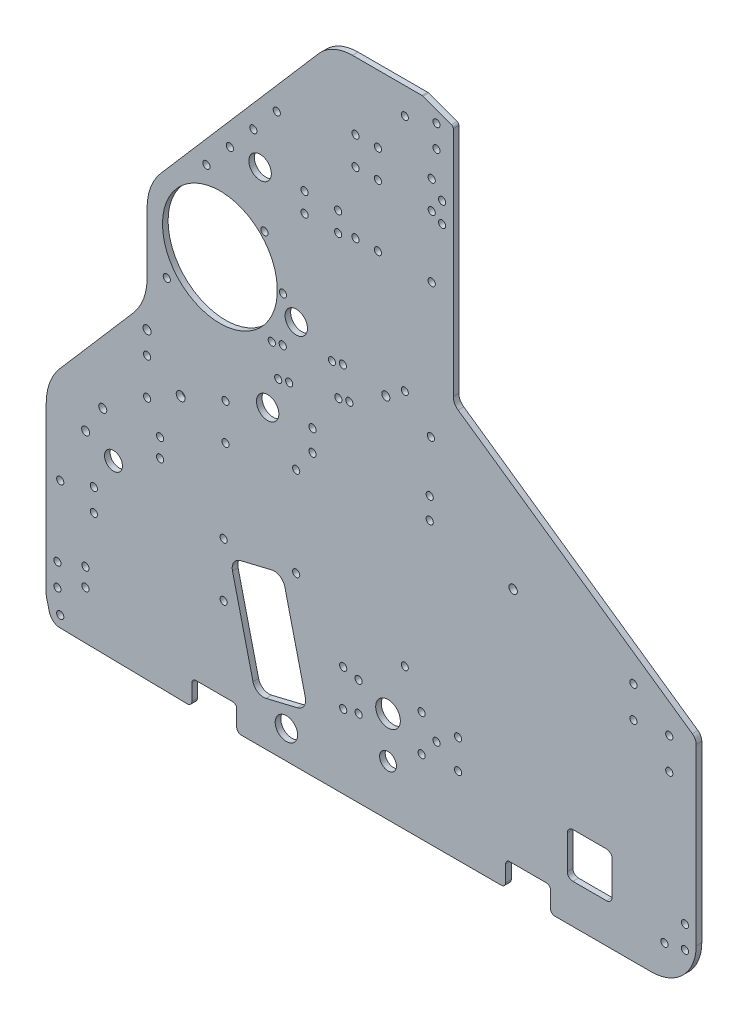
SolidWorks part; units mm, degrees
ref_plane "Front Plane" through (0, 0, 0) normal (0, 0, 1) x (1, 0, 0)
ref_plane "Top Plane" through (0, 0, 0) normal (0, 1, 0) x (1, 0, 0)
ref_plane "Right Plane" through (0, 0, 0) normal (1, 0, 0) x (0, 0, -1)
sketch "Sketch1" plane through (0, 0, 0) normal (0, 0, 1) x (1, 0, 0)
  line L0 (82.55, -20.32) -> (82.55, -6.35)
  line L2 (0, 0) -> (0, 157.48)
  line L4 (368.3, -20.32) -> (368.3, 106.68)
  line L5 (82.55, -6.35) -> (107.95, -6.35)
  line L6 (107.95, -6.35) -> (107.95, -20.32)
  line L7 (107.95, -20.32) -> (260.35, -20.32)
  line L8 (260.35, -20.32) -> (260.35, -6.35)
  line L9 (260.35, -6.35) -> (285.75, -6.35)
  line L10 (285.75, -6.35) -> (285.75, -20.32)
  line L11 (285.75, -20.32) -> (368.3, -20.32)
  line L12 (361.95, 12.7) -> (368.3, 12.7) construction
  line L13 (0, 0) -> (6.35, 0) construction
  line L14 (0.1896, -7.8901) -> (1.7771, -14.2401)
  line L15 (7.8295, -19.0491) -> (82.55, -20.32)
  line L16 (0, 0) -> (0, -6.35)
  line L17 (76.2, 128.905) -> (79.375, 128.905) construction
  line L18 (57.15, 118.5863) -> (101.6, 118.5862) construction
  line L19 (57.15, 118.5863) -> (57.15, 139.2238) construction
  line L20 (101.6, 118.5862) -> (101.6, 139.2237) construction
  line L21 (57.15, 139.2238) -> (101.6, 139.2237) construction
  line L22 (57.15, 118.5863) -> (101.6, 139.2237) construction
  line L23 (101.6, 118.5862) -> (57.15, 139.2238) construction
  line L24 (101.6, 139.2237) -> (125.4682, 147.9111) construction
  line L25 (203.2, 59.805) -> (203.2, 194.805) construction
  line L26 (203.2, 194.805) -> (203.2, 329.805) construction
  line L27 (355.6, 332.105) -> (330.2, 332.105) construction
  line L28 (330.2, 332.105) -> (330.2, 217.805) construction
  line L29 (330.2, 217.805) -> (355.6, 217.805) construction
  line L30 (355.6, 217.805) -> (355.6, 332.105) construction
  line L31 (203.2, 344.805) -> (203.2, 194.805) construction
  line L32 (50.8, 332.105) -> (76.2, 332.105) construction
  line L33 (76.2, 332.105) -> (76.2, 217.805) construction
  line L34 (50.8, 217.805) -> (50.8, 332.105) construction
  line L35 (76.2, 217.805) -> (50.8, 217.805) construction
  line L36 (213.2, 344.805) -> (230.6638, 338.455)
  line L37 (203.2, 344.805) -> (161.925, 344.805)
  line L38 (203.2, 344.805) -> (213.2, 344.805)
  line L39 (348.5362, 344.805) -> (413.4623, 344.805)
  line L40 (348.5362, 344.805) -> (230.6638, 344.805) construction
  line L42 (161.925, 344.805) -> (0, 157.48)
  line L44 (230.6638, 338.455) -> (230.6638, 202.565)
  line L45 (230.6638, 202.565) -> (368.3, 106.68)
  line L46 (213.2, 344.805) -> (-141.0713, 344.805) construction
  line L47 (350.3395, -2.3595) -> (368.3, -20.32) construction
  circle A0 centre (6.35, 0) radius 2.032
  circle A1 centre (6.35, 12.7) radius 2.032
  circle A2 centre (361.95, 0) radius 2.032
  circle A3 centre (361.95, 12.7) radius 2.032
  arc A5 (1.7771, -14.2401) -> (7.8295, -19.0491) centre (7.9375, -12.7) ccw
  circle A6 centre (7.9375, -12.7) radius 2.032
  arc A7 (0, -6.35) -> (0.1896, -7.8901) centre (6.35, -6.35) ccw
  circle A8 centre (38.1, 78.105) radius 5.08
  circle A9 centre (76.2, 128.905) radius 2.54
  circle A10 centre (101.6, 118.5862) radius 2.032
  circle A11 centre (101.6, 139.2237) radius 2.032
  circle A12 centre (57.15, 139.2238) radius 2.032
  circle A13 centre (57.15, 118.5863) radius 2.032
  circle A15 centre (203.2, 59.805) radius 2
  circle A16 centre (203.2, 194.805) radius 2
  circle A17 centre (203.2, 329.805) radius 2
  circle A18 centre (63.5, 313.055) radius 2.032
  circle A20 centre (355.6, 332.105) radius 2.032
  circle A21 centre (330.2, 332.105) radius 2.032
  circle A22 centre (355.6, 217.805) radius 2.032
  circle A23 centre (330.2, 217.805) radius 2.032
  circle A24 centre (50.8, 332.105) radius 2.032
  circle A25 centre (76.2, 332.105) radius 2.032
  circle A26 centre (50.8, 217.805) radius 2.032
  circle A27 centre (76.2, 217.805) radius 2.032
  circle A28 centre (221.1381, 335.28) radius 2
  circle A29 centre (224.3138, 298.831) radius 2.032
  circle A30 centre (353.06, 100.7351) radius 2.032
  circle A31 centre (332.74, 115.9751) radius 2.032
  circle A32 centre (332.74, 98.1951) radius 2.032
  circle A33 centre (353.06, 82.9551) radius 2.032
  circle A34 centre (117.3562, 280.4276) radius 2.032
  circle A35 centre (104.0678, 265.0548) radius 2.032
  circle A36 centre (90.7795, 249.682) radius 2.032
  circle A38 centre (130.6445, 295.8004) radius 2.032
  circle A39 centre (68.326, 182.9237) radius 2.032
  circle A40 centre (224.3138, 287.401) radius 2.032
  circle A41 centre (125.4682, 147.9111) radius 6.35
  circle A42 centre (221.1381, 322.58) radius 2
  circle A43 centre (350.3395, -2.3595) radius 2.032
  point P82 (203.2, 344.805)
  point P90 (368.3, 62.484)
  dimension "D6" = 4.064
  dimension "D10" = 6.35
  dimension "D11" = 4.064
  dimension "D17" = 38.1
  dimension "D27" = 4
  dimension "D31" = 4.064
  dimension "D32" = 41.275
  dimension "D36" = 4.064
  dimension "D47" = 39.624
  dimension "D48" = 4.064
  dimension "D25" = 5.08
  dimension "D26" = 4.064
  dimension "D52" = 4.064
  dimension "D65" = 4.064
  dimension "D69" = 10.16
  dimension "D72" = 12.7
  dimension "D2" = 127
  dimension "D3" = 13.97
  dimension "D4" = 25.4
  dimension "D5" = 152.4
  dimension "D7" = 12.7
  dimension "D8" = 6.35
  dimension "D9" = 20.32
  dimension "D12" = 12.7
  dimension "D13" = 1.5875
  dimension "D14" = 82.55
  dimension "D15" = 368.3
  dimension "D16" = 6.35
  dimension "D18" = 98.425
  dimension "D19" = 38.1
  dimension "D20" = 50.8
  dimension "D21" = 3.175
  dimension "D22" = 270
  dimension "D23" = 20.6375
  dimension "D24" = 44.45
  dimension "D28" = 135
  dimension "D29" = 12.7
  dimension "D30" = 15
  dimension "D33" = 63.5
  dimension "D34" = 27.4638
  dimension "D35" = 12.7
  dimension "D37" = 114.3
  dimension "D38" = 25.4
  dimension "D39" = 12.7
  dimension "D40" = 157.48
  dimension "D41" = 142.24
  dimension "D42" = 365.125
  dimension "D43" = 10
  dimension "D44" = 6.35
  dimension "D45" = 31.75
  dimension "D46" = 3.175
  dimension "D49" = 6.35
  dimension "D50" = 203.2
  dimension "D51" = 15.24
  dimension "D53" = 17.78
  dimension "D54" = 17.78
  dimension "D55" = 20.32
  dimension "D56" = 15.24
  dimension "D57" = 92.202
  dimension "D58" = 8.382
  dimension "D59" = 20.32
  dimension "D60" = 20.32
  dimension "D61" = 8.382
  dimension "D62" = 20.32
  dimension "D63" = 8.382
  dimension "D64" = 8.382
  dimension "D66" = 35.052
  dimension "D67" = 68.326
  dimension "D68" = 11.43
  dimension "D70" = 25.4
  dimension "D71" = 110
  dimension "D73" = 17.9381
  dimension "D74" = 12.7
  dimension "D75" = 45
  dimension "D76" = 25.4
extrude "Boss-Extrude1" add sketch "Sketch1" along normal blind 3.175 contours L16 A7 L14 A5 L15 L2 A0 A1 A6 region at (171.4792, 119.5149, 0)
fillet "Fillet1" radius 2.286 4 edges at (285.75, -6.35, 1.5875) (107.95, -6.35, 1.5875) (260.35, -6.35, 1.5875) (82.55, -6.35, 1.5875)
fillet "Fillet2" radius 6.35 1 edges at (230.6638, 202.565, 1.5875)
sketch "Sketch2" plane through (0, 0, 0) normal (0, 0, -1) x (-1, 0, 0)
  circle A0 centre (-100.5528, 71.086) radius 2.032 construction
  circle A1 centre (-100.5528, 40.606) radius 2.032 construction
  circle A2 centre (-22.225, 18.2025) radius 2.032 construction
  circle A3 centre (-22.225, 8.0425) radius 2.032 construction
  circle A4 centre (-100.5528, 71.086) radius 2.032
  circle A5 centre (-100.5528, 40.606) radius 2.032
  circle A6 centre (-22.225, 18.2025) radius 2.032
  circle A7 centre (-22.225, 8.0425) radius 2.032
extrude "Cut-Extrude1" cut sketch "Sketch2" against normal through all
fillet "Fillet3" radius 1.5875 2 edges at (230.6638, 338.455, 1.5875) (213.2, 344.805, 1.5875)
sketch "Sketch3" plane through (0, 0, 3.175) normal (0, 0, 1) x (1, 0, 0)
  line L0 (132.9524, 63.2646) -> (132.7215, 64.2281) construction
  line L1 (128.3814, 66.8897) -> (110.6828, 62.6472) construction
  line L2 (114.5132, 58.4237) -> (126.8822, 61.3887) construction
  line L3 (108.0212, 58.3071) -> (108.2522, 57.3436) construction
  line L4 (131.2006, 57.703) -> (140.0164, 20.9265) construction
  line L5 (144.0993, 16.7636) -> (132.9524, 63.2646) construction
  line L6 (108.2522, 57.3436) -> (119.3991, 10.8426) construction
  line L7 (121.1509, 16.4042) -> (112.3351, 53.1807) construction
  line L8 (119.3991, 10.8426) -> (119.6301, 9.8791) construction
  line L9 (144.3303, 15.8001) -> (144.0993, 16.7636) construction
  line L10 (137.8383, 15.6835) -> (125.4694, 12.7185) construction
  line L11 (123.9701, 7.2175) -> (141.6687, 11.4601) construction
  line L12 (132.9524, 63.2646) -> (132.7215, 64.2281)
  line L13 (128.3814, 66.8897) -> (110.6828, 62.6472)
  line L14 (114.5132, 58.4237) -> (126.8822, 61.3887)
  line L15 (108.0212, 58.3071) -> (108.2522, 57.3436)
  line L16 (131.2006, 57.703) -> (140.0164, 20.9265)
  line L17 (144.0993, 16.7636) -> (132.9524, 63.2646)
  line L18 (108.2522, 57.3436) -> (119.3991, 10.8426)
  line L19 (121.1509, 16.4042) -> (112.3351, 53.1807)
  line L20 (119.3991, 10.8426) -> (119.6301, 9.8791)
  line L21 (144.3303, 15.8001) -> (144.0993, 16.7636)
  line L22 (137.8383, 15.6835) -> (125.4694, 12.7185)
  line L23 (123.9701, 7.2175) -> (141.6687, 11.4601)
  line L24 (127.7894, 69.3598) -> (110.0908, 65.1172)
  line L25 (105.5512, 57.715) -> (105.7822, 56.7515)
  line L26 (105.7822, 56.7515) -> (116.9291, 10.2505)
  line L27 (116.9291, 10.2505) -> (117.16, 9.287)
  line L28 (124.5622, 4.7475) -> (142.2608, 8.99)
  line L29 (146.8003, 16.3922) -> (146.5694, 17.3557)
  line L30 (146.5694, 17.3557) -> (135.4225, 63.8567)
  line L31 (135.4225, 63.8567) -> (135.1915, 64.8202)
  line L32 (14.605, -0.1369) -> (103.7278, 32.3011) construction
  line L33 (14.605, -0.1369) -> (103.7278, 32.3011)
  line L34 (0, -6.35) -> (0, 157.48) construction
  line L35 (-39.6666, 74.7152) -> (103.7278, 126.9065) construction
  line L36 (26.9875, 46.9531) -> (26.9875, 59.6531) construction
  line L37 (107.95, -20.32) -> (260.35, -20.32) construction
  line L38 (64.5259, 92.5258) -> (64.5259, 102.9405) construction
  line L39 (131.6538, 14.201) -> (136.0946, -4.3242) construction
  arc A0 (132.7215, 64.2281) -> (128.6308, 66.9403) centre (129.2206, 63.3889) ccw construction
  arc A1 (110.6828, 62.6472) -> (110.4377, 62.5791) centre (111.522, 59.1463) ccw construction
  arc A2 (128.6308, 66.9403) -> (128.3814, 66.8897) centre (129.2206, 63.3889) ccw construction
  arc A3 (110.4377, 62.5791) -> (108.0212, 58.3071) centre (111.522, 59.1463) ccw construction
  arc A4 (119.6301, 9.8791) -> (123.7207, 7.1669) centre (123.1309, 10.7183) ccw construction
  arc A5 (141.9139, 11.5281) -> (144.3303, 15.8001) centre (140.8295, 14.9609) ccw construction
  arc A6 (141.6687, 11.4601) -> (141.9139, 11.5281) centre (140.8295, 14.9609) ccw construction
  arc A7 (123.7207, 7.1669) -> (123.9701, 7.2175) centre (123.1309, 10.7183) ccw construction
  arc A8 (132.7215, 64.2281) -> (128.6308, 66.9403) centre (129.2206, 63.3889) ccw
  arc A9 (110.6828, 62.6472) -> (110.4377, 62.5791) centre (111.522, 59.1463) ccw
  arc A10 (128.6308, 66.9403) -> (128.3814, 66.8897) centre (129.2206, 63.3889) ccw
  arc A11 (110.4377, 62.5791) -> (108.0212, 58.3071) centre (111.522, 59.1463) ccw
  arc A12 (119.6301, 9.8791) -> (123.7207, 7.1669) centre (123.1309, 10.7183) ccw
  arc A13 (141.9139, 11.5281) -> (144.3303, 15.8001) centre (140.8295, 14.9609) ccw
  arc A14 (141.6687, 11.4601) -> (141.9139, 11.5281) centre (140.8295, 14.9609) ccw
  arc A15 (123.7207, 7.1669) -> (123.9701, 7.2175) centre (123.1309, 10.7183) ccw
  arc A16 (110.0908, 65.1172) -> (109.6726, 65.0012) centre (111.522, 59.1463) ccw
  arc A17 (109.6726, 65.0012) -> (105.5512, 57.715) centre (111.522, 59.1463) ccw
  arc A18 (117.16, 9.287) -> (124.1369, 4.6613) centre (123.1309, 10.7183) ccw
  arc A19 (124.1369, 4.6613) -> (124.5622, 4.7475) centre (123.1309, 10.7183) ccw
  arc A20 (142.2608, 8.99) -> (142.6789, 9.1061) centre (140.8295, 14.9609) ccw
  arc A21 (142.6789, 9.1061) -> (146.8003, 16.3922) centre (140.8295, 14.9609) ccw
  arc A22 (135.1915, 64.8202) -> (128.2147, 69.446) centre (129.2206, 63.3889) ccw
  arc A23 (128.2147, 69.446) -> (127.7894, 69.3598) centre (129.2206, 63.3889) ccw
  circle A24 centre (136.0946, -4.3242) radius 6.35
  circle A26 centre (134.1438, 208.2281) radius 2.032 construction
  circle A33 centre (26.9875, 46.9531) radius 2.032
  circle A34 centre (26.9875, 59.6531) radius 2.032
  circle A35 centre (7.9375, 53.3031) radius 2.032
  circle A37 centre (32.0306, 100.8109) radius 32.385 construction
  circle A38 centre (32.0306, 100.8109) radius 2.286
  circle A39 centre (123.682, 233.4851) radius 2.032 construction
  circle A40 centre (64.5259, 102.9405) radius 2.032
  circle A41 centre (64.5259, 92.5258) radius 2.032
  circle A42 centre (134.1438, 208.2281) radius 2.032
  circle A43 centre (123.682, 233.4851) radius 2.032
  ellipse E0 centre (124.5974, 48.8487) end of major axis (128.5376, 61.3578) minor radius 6 (131.2006, 57.703) -> (126.8822, 61.3887) ccw construction
  ellipse E1 centre (122.2349, 48.2824) end of major axis (113.0518, 57.6456) minor radius 6 (114.5132, 58.4237) -> (112.3351, 53.1807) ccw construction
  ellipse E2 centre (127.7541, 25.2585) end of major axis (131.6942, 37.7675) minor radius 6 (121.1509, 16.4042) -> (125.4694, 12.7185) ccw construction
  ellipse E3 centre (130.1166, 25.8248) end of major axis (139.2998, 16.4616) minor radius 6 (137.8383, 15.6835) -> (140.0164, 20.9265) ccw construction
  ellipse E4 centre (124.5974, 48.8487) end of major axis (128.5376, 61.3578) minor radius 6 (131.2006, 57.703) -> (126.8822, 61.3887) ccw
  ellipse E5 centre (122.2349, 48.2824) end of major axis (131.4181, 38.9192) minor radius 6 (114.5132, 58.4237) -> (112.3351, 53.1807) ccw
  ellipse E6 centre (127.7541, 25.2585) end of major axis (123.8139, 12.7495) minor radius 6 (121.1509, 16.4042) -> (125.4694, 12.7185) ccw
  ellipse E7 centre (130.1166, 25.8248) end of major axis (139.2998, 16.4616) minor radius 6 (137.8383, 15.6835) -> (140.0164, 20.9265) ccw
  point P93 (26.9875, 53.3031)
  point P115 (32.0306, 100.8109)
  dimension "D3" = 64.77
  dimension "D4" = 4.572
  dimension "D8" = 4.064
  dimension "D13" = 12.7
  dimension "D2" = 88.9
  dimension "D5" = 7.9375
  dimension "D6" = 19.05
  dimension "D7" = 73.6231
  dimension "D9" = 12.7
  dimension "D10" = 10.4147
  dimension "D11" = 37.5384
  dimension "D12" = 45.5727
  dimension "D14" = 19.05
  dimension "D1" = 2.54
extrude "Cut-Extrude2" cut sketch "Sketch3" against normal through all contours A22 A23 L24 A16 A17 L25 L26 L27 A18 A19 L28 A20 A21 L29 L30 L31 A15 A12 L20 L18 L15 A11 A9 L13 A10 A8 L12 L17 L21 A13 A14 L23 | A12 A15 L23 A14 A13 L21 L17 L12 A8 A10 L13 A9 A11 L15 L18 L20 E7 L22 E6 L19 E5 L14 E4 L16 | L22 E7 L16 E4 L14 E5 L19 E6 | A38 | A41 | A40 | A35 | A34 | A33 | A43 | A42 | A24 region at (137.844, 39.8506, 3.175) region at (126.1758, 37.0536, 3.175) region at (128.1544, 68.6507, 3.175) region at (32.0306, 100.8109, 3.175) region at (64.5259, 102.9405, 3.175) region at (64.5259, 92.5258, 3.175)
sketch "Sketch4" plane through (0, 0, 3.175) normal (0, 0, 1) x (1, 0, 0)
  line L0 (57.15, 139.2238) -> (101.6, 139.2237) construction
  line L1 (168.275, 21.4312) -> (212.725, 21.4312) construction
  line L2 (168.275, 21.4312) -> (168.275, 42.0687) construction
  line L3 (168.275, 42.0687) -> (212.725, 42.0687) construction
  line L4 (212.725, 21.4312) -> (212.725, 42.0687) construction
  line L5 (168.275, 21.4312) -> (212.725, 42.0687) construction
  line L6 (168.275, 42.0687) -> (212.725, 21.4312) construction
  line L7 (57.15, 118.5863) -> (57.15, 139.2238) construction
  line L8 (107.95, -20.32) -> (260.35, -20.32) construction
  line L9 (193.675, 31.75) -> (177.005, 31.75) construction
  line L10 (190.5, 31.75) -> (193.675, 31.75) construction
  line L11 (6.35, 12.7) -> (361.95, 12.7) construction
  line L12 (107.95, -6.35) -> (107.95, -20.32) construction
  line L13 (193.675, 31.75) -> (220.6625, 31.75) construction
  line L14 (177.005, 23.4569) -> (177.005, 40.0431) construction
  line L15 (213.2, 44.805) -> (193.2, 44.805) construction
  line L16 (213.2, 44.805) -> (213.2, 344.805) construction
  line L17 (213.2, 344.805) -> (193.2, 344.805) construction
  line L18 (193.2, 44.805) -> (193.2, 344.805) construction
  line L19 (213.2, 44.805) -> (193.2, 344.805) construction
  line L20 (213.2, 344.805) -> (193.2, 44.805) construction
  line L21 (226.1381, 335.28) -> (226.1381, 31.75) construction
  line L22 (237.33, 40.0431) -> (233.3612, 40.0431) construction
  line L23 (237.33, 23.4569) -> (233.3612, 23.4569) construction
  circle A0 centre (168.275, 42.0687) radius 2.032
  circle A1 centre (212.725, 42.0687) radius 2.032
  circle A2 centre (212.725, 21.4312) radius 2.032
  circle A3 centre (168.275, 21.4312) radius 2.032
  circle A4 centre (193.675, 31.75) radius 6.985
  circle A7 centre (220.6625, 31.75) radius 14.2875 construction
  circle A8 centre (193.675, 31.75) radius 12.7 construction
  circle A9 centre (177.005, 40.0431) radius 2.032
  circle A10 centre (177.005, 23.4569) radius 2.032
  circle A11 centre (237.33, 40.0431) radius 2.032 construction
  circle A12 centre (237.33, 23.4569) radius 2.032 construction
  circle A13 centre (193.675, 8.4667) radius 4.7625
  circle A14 centre (221.1381, 31.75) radius 2.032
  circle A15 centre (221.1381, 31.75) radius 5 construction
  circle A16 centre (221.1381, 335.28) radius 5 construction
  circle A17 centre (233.3612, 23.4569) radius 2.032
  circle A18 centre (233.3612, 40.0431) radius 2.032
  point P0 (190.5, 31.75)
  point P26 (203.2, 194.805)
  point P38 (177.005, 31.75)
  dimension "D1" = 4.064
  dimension "D4" = 13.97
  dimension "D7" = 9.525
  dimension "D10" = 25.4
  dimension "D11" = 28.575
  dimension "D16" = 10
  dimension "D17" = 4.064
  dimension "D18" = 10
  dimension "D2" = 52.07
  dimension "D3" = 3.175
  dimension "D5" = 82.55
  dimension "D6" = 26.9875
  dimension "D8" = 20
  dimension "D9" = 300
  dimension "D12" = 16.67
  dimension "D13" = 16.5862
  dimension "D14" = 60.325
  dimension "D15" = 23.2833
  dimension "D19" = 3.9688
extrude "Cut-Extrude3" cut sketch "Sketch4" against normal through all
sketch "Sketch5" plane through (0, 0, 0) normal (0, 0, -1) x (-1, 0, 0)
  line L0 (-57.15, 223.5947) -> (-57.15, 165.3337)
  line L1 (-161.925, 344.805) -> (-52.7201, 218.4699) construction
  line L2 (-57.15, 165.3337) -> (0, 99.219)
  line L3 (0, -6.35) -> (0, 157.48) construction
  line L4 (-147.864, -30.311) -> (-147.864, -16.0874)
  line L5 (-50.4199, 215.8089) -> (0, 157.48) construction
  line L6 (-57.15, 223.5947) -> (0, 157.48)
  line L7 (0, 157.48) -> (0, 99.219)
  line L8 (-98.425, 208.2281) -> (-141.6756, 197.9719) construction
  circle A0 centre (-98.425, 208.2281) radius 32.5437
  circle A1 centre (-141.6756, 197.9719) radius 6.35
  circle A3 centre (-264.5736, 128.3328) radius 2.39
  dimension "D3" = 65.0875
  dimension "D7" = 12.7
  dimension "D8" = 4.78
  dimension "D1" = 38.1
  dimension "D2" = 57.15
  dimension "D4" = 41.275
  dimension "D5" = 41.275
  dimension "D9" = 22.2382
  dimension "D10" = 117.7733
  dimension "D11" = 11.6447
  dimension "D12" = 123.5853
  dimension "D14" = 62.5
  dimension "D13" = 44.45
extrude "Cut-Extrude5" cut sketch "Sketch5" against normal through all contours A0 | L7 L6 L0 L2 | A3 | A1 region at (28.575, 161.4068, 0) region at (98.425, 208.2281, 0) region at (264.5736, 128.3328, 0)
fillet "Fillet4" radius 31.75 3 edges at (0, 99.219, 1.5875) (57.15, 165.3337, 1.5875) (57.15, 223.5947, 1.5875)
sketch "Sketch6" plane through (0, 0, 3.175) normal (0, 0, 1) x (1, 0, 0)
  line L0 (285.75, -20.32) -> (368.3, -20.32) construction
  line L1 (298.45, 27.305) -> (317.5, 27.305)
  line L2 (295.275, 24.13) -> (295.275, 5.08)
  line L3 (298.45, 1.905) -> (317.5, 1.905)
  line L4 (320.675, 24.13) -> (320.675, 5.08)
  line L5 (295.275, 27.305) -> (320.675, 1.905) construction
  line L6 (295.275, 1.905) -> (320.675, 27.305) construction
  line L7 (368.3, -20.32) -> (368.3, 106.68) construction
  arc A0 (295.275, 5.08) -> (298.45, 1.905) centre (298.45, 5.08) ccw
  arc A1 (317.5, 1.905) -> (320.675, 5.08) centre (317.5, 5.08) ccw
  arc A2 (317.5, 27.305) -> (320.675, 24.13) centre (317.5, 24.13) cw
  arc A3 (298.45, 27.305) -> (295.275, 24.13) centre (298.45, 24.13) ccw
  point P0 (307.975, 14.605)
  dimension "D2" = 3.175
  dimension "D1" = 25.4
  dimension "D3" = 22.225
  dimension "D4" = 47.625
extrude "Cut-Extrude6" cut sketch "Sketch6" against normal through all
fillet "Fillet5" radius 25.4 1 edges at (161.925, 344.805, 1.5875)
sketch "Sketch8" plane through (0, 0, 0) normal (0, 0, -1) x (-1, 0, 0)
  line L0 (-230.6638, 337.343) -> (-230.6638, 205.8802) construction
  line L1 (-230.6638, 255.905) -> (-175.26, 255.905) construction
  line L2 (-175.26, 255.905) -> (-175.26, 306.705) construction
  line L3 (-175.26, 306.705) -> (-230.6638, 306.705) construction
  line L4 (-173.5432, 344.805) -> (-212.9203, 344.805) construction
  line L7 (-107.95, -20.32) -> (-260.35, -20.32) construction
  circle A0 centre (-218.44, 290.83) radius 3.9687
  circle A1 centre (-218.44, 290.83) radius 2.032
  circle A2 centre (218.44, 265.7972) radius 3.9687
  circle A3 centre (218.44, 265.7972) radius 2.032
  circle A4 centre (-205.74, 290.83) radius 3.9687
  circle A5 centre (-205.74, 290.83) radius 2.032
  circle A6 centre (-187.96, 290.83) radius 3.9687
  circle A7 centre (-187.96, 290.83) radius 2.032
  circle A8 centre (-187.96, 306.705) radius 2.032
  circle A9 centre (-175.26, 290.83) radius 3.9687
  circle A10 centre (-175.26, 290.83) radius 2.032
  circle A11 centre (-205.74, 306.705) radius 2.032
  circle A13 centre (-205.74, 255.905) radius 2.032
  circle A14 centre (-187.96, 255.905) radius 2.032
  circle A16 centre (-218.44, 306.705) radius 2.032
  circle A17 centre (-175.26, 306.705) radius 2.032
  circle A18 centre (-175.26, 255.905) radius 2.032
  circle A19 centre (-218.44, 255.905) radius 2.032
  circle A20 centre (-218.44, 306.705) radius 3.9687
  circle A21 centre (-205.74, 306.705) radius 3.9687
  circle A22 centre (-175.26, 306.705) radius 3.9687
  circle A23 centre (-218.44, 255.905) radius 3.9687
  circle A24 centre (-205.74, 255.905) radius 3.9687
  circle A25 centre (-187.96, 255.905) radius 3.9687
  circle A26 centre (-175.26, 255.905) radius 3.9687
  circle A27 centre (-187.96, 306.705) radius 3.9687
  dimension "D1" = 7.9375
  dimension "D7" = 4.064
  dimension "D13" = 12.2237
  dimension "D2" = 12.2237
  dimension "D3" = 12.7
  dimension "D4" = 17.78
  dimension "D5" = 12.7
  dimension "D6" = 88.9
  dimension "D8" = 38.1
  dimension "D9" = 17.78
  dimension "D10" = 12.7
  dimension "D11" = 55.4037
  dimension "D12" = 12.7
  dimension "D14" = 311.15
extrude "Cut-Extrude7" cut sketch "Sketch8" against normal through all contours A16 | A17 | A18 | A19 | A8 | A14 | A1 | A7 | A10 region at (218.44, 306.705, 0) region at (175.26, 306.705, 0) region at (175.26, 255.905, 0) region at (218.44, 255.905, 0)
sketch "Sketch10" plane through (0, 0, 3.175) normal (0, 0, 1) x (1, 0, 0)
  circle A4 centre (141.6425, 74.6844) radius 2.032 construction
  circle A5 centre (141.6425, 125.4844) radius 2.032 construction
  circle A6 centre (141.6425, 74.6844) radius 2.032
  circle A7 centre (141.6425, 125.4844) radius 2.032
extrude "Cut-Extrude8" cut sketch "Sketch10" against normal through all
sketch "Sketch11" plane through (0, 0, 3.175) normal (0, 0, 1) x (1, 0, 0)
  ellipse E4 centre (150.8814, 138.43) end of major axis (150.8814, 140.462) minor radius 2.032
  ellipse E5 centre (150.8814, 150.495) end of major axis (150.8814, 152.527) minor radius 2.032
  ellipse E6 centre (217.3024, 150.495) end of major axis (217.3024, 152.527) minor radius 2.032
  ellipse E7 centre (217.3024, 138.43) end of major axis (217.3024, 140.462) minor radius 2.032
extrude "Cut-Extrude9" cut sketch "Sketch11" against normal through all
sketch "Sketch12" plane through (0, 0, 0) normal (0, 0, -1) x (-1, 0, 0)
  line L0 (-173.5432, 344.805) -> (-212.9203, 344.805) construction
  circle A0 centre (-165.4175, 264.635) radius 2.032
  circle A1 centre (-203.2, 329.805) radius 2 construction
  circle A2 centre (-165.4175, 253.5225) radius 2.032
  circle A3 centre (-146.3675, 253.5225) radius 2.032
  circle A4 centre (-146.3675, 264.635) radius 2.032
  dimension "D1" = 80.17
  dimension "D2" = 4.064
  dimension "D3" = 37.7825
  dimension "D4" = 11.1125
  dimension "D5" = 19.05
extrude "Cut-Extrude10" cut sketch "Sketch12" against normal through all
sketch "Sketch14" plane through (0, 0, 0) normal (0, 0, -1) x (-1, 0, 0)
  line L0 (-130.6445, 295.8004) -> (-121.1847, 263.6885) construction
  line L1 (-121.1847, 263.6885) -> (-90.7795, 249.682) construction
  line L2 (-154.3272, 336.0154) -> (-64.88, 232.5373) construction
  line L4 (-118.517, 269.4796) -> (-115.3937, 261.0208) construction
  line L5 (-118.517, 269.4796) -> (-126.9758, 266.3562) construction
  line L6 (-126.9758, 266.3562) -> (-123.8524, 257.8974) construction
  line L7 (-115.3937, 261.0208) -> (-123.8524, 257.8974) construction
  line L8 (-118.517, 269.4796) -> (-123.8524, 257.8974) construction
  line L9 (-126.9758, 266.3562) -> (-115.3937, 261.0208) construction
  circle A0 centre (-121.1847, 263.6885) radius 6.376
  dimension "D1" = 22.225
  dimension "D2" = 9.017
extrude "Cut-Extrude11" cut sketch "Sketch14" against normal through all
sketch "Sketch15" plane through (0, 0, 3.175) normal (0, 0, 1) x (1, 0, 0)
  line L0 (38.1, 78.105) -> (35.0376, 98.2034) construction
  line L1 (20.5874, 75.6997) -> (81.7263, 75.6997) construction
  line L2 (57.15, 139.2237) -> (57.15, 151.9237) construction
  line L3 (52.4937, 153.9549) -> (22.3594, 84.8727) construction
  line L4 (56.0505, 156.8833) -> (192.439, 187.1199) construction
  line L5 (52.4937, 153.9549) -> (37.8292, 107.1192) construction
  line L6 (20.5874, 75.6997) -> (38.1, 78.105) construction
  line L7 (35.0376, 98.2034) -> (37.8292, 107.1192) construction
  line L8 (20.5874, 75.6997) -> (22.3594, 84.8727) construction
  line L9 (38.1, 78.105) -> (17.7696, 78.105) construction
  line L10 (17.7696, 78.105) -> (21.6585, 86.5997) construction
  line L11 (21.6585, 86.5997) -> (52.4937, 153.9549) construction
  circle A0 centre (20.5874, 75.6997) radius 2.159 construction
  circle A1 centre (20.5874, 75.6997) radius 2.159 construction
  circle A2 centre (57.15, 139.2237) radius 2.032 construction
  circle A3 centre (57.15, 139.2237) radius 2.032 construction
  circle A4 centre (57.15, 151.9237) radius 2.286
  circle A5 centre (192.439, 187.1199) radius 2.286
  circle A6 centre (57.15, 151.9237) radius 5.08 construction
  circle A7 centre (38.1, 78.105) radius 2.159 construction
  circle A8 centre (38.1, 78.105) radius 2.159
  arc A9 (163.8737, 173.6806) -> (164.5125, 170.7993) centre (165.557, 172.5423) ccw construction
  arc A10 (173.4397, 172.7784) -> (172.801, 175.6597) centre (171.7565, 173.9167) ccw construction
  arc A11 (172.801, 175.6597) -> (173.4397, 172.7784) centre (171.7565, 173.9167) ccw construction
  arc A12 (164.5125, 170.7993) -> (163.8737, 173.6806) centre (165.557, 172.5423) ccw construction
  arc A13 (169.1588, 192.0883) -> (169.7976, 189.2071) centre (168.1143, 190.3453) ccw construction
  arc A14 (169.7976, 189.2071) -> (169.1588, 192.0883) centre (168.1143, 190.3453) ccw construction
  arc A15 (160.2316, 190.1092) -> (160.8704, 187.2279) centre (161.9149, 188.9709) ccw construction
  arc A16 (160.8704, 187.2279) -> (160.2316, 190.1092) centre (161.9149, 188.9709) ccw construction
  arc A17 (129.7766, 166.1214) -> (130.4154, 163.2402) centre (131.4599, 164.9832) ccw construction
  arc A18 (139.3426, 165.2193) -> (138.7038, 168.1005) centre (137.6593, 166.3576) ccw construction
  arc A19 (138.7038, 168.1005) -> (139.3426, 165.2193) centre (137.6593, 166.3576) ccw construction
  arc A20 (130.4154, 163.2402) -> (129.7766, 166.1214) centre (131.4599, 164.9832) ccw construction
  arc A21 (135.7005, 181.6479) -> (135.0617, 184.5292) centre (134.0172, 182.7862) ccw construction
  arc A22 (135.0617, 184.5292) -> (135.7005, 181.6479) centre (134.0172, 182.7862) ccw construction
  arc A23 (126.1345, 182.55) -> (126.7732, 179.6688) centre (127.8177, 181.4118) ccw construction
  arc A24 (126.7732, 179.6688) -> (126.1345, 182.55) centre (127.8177, 181.4118) ccw construction
  arc A25 (163.8737, 173.6806) -> (164.5125, 170.7993) centre (165.557, 172.5423) ccw
  arc A26 (173.4397, 172.7784) -> (172.801, 175.6597) centre (171.7565, 173.9167) ccw
  arc A27 (172.801, 175.6597) -> (173.4397, 172.7784) centre (171.7565, 173.9167) ccw
  arc A28 (164.5125, 170.7993) -> (163.8737, 173.6806) centre (165.557, 172.5423) ccw
  arc A29 (169.1588, 192.0883) -> (169.7976, 189.2071) centre (168.1143, 190.3453) ccw
  arc A30 (169.7976, 189.2071) -> (169.1588, 192.0883) centre (168.1143, 190.3453) ccw
  arc A31 (160.2316, 190.1092) -> (160.8704, 187.2279) centre (161.9149, 188.9709) ccw
  arc A32 (160.8704, 187.2279) -> (160.2316, 190.1092) centre (161.9149, 188.9709) ccw
  arc A33 (129.7766, 166.1214) -> (130.4154, 163.2402) centre (131.4599, 164.9832) ccw
  arc A34 (139.3426, 165.2193) -> (138.7038, 168.1005) centre (137.6593, 166.3576) ccw
  arc A35 (138.7038, 168.1005) -> (139.3426, 165.2193) centre (137.6593, 166.3576) ccw
  arc A36 (130.4154, 163.2402) -> (129.7766, 166.1214) centre (131.4599, 164.9832) ccw
  arc A37 (135.7005, 181.6479) -> (135.0617, 184.5292) centre (134.0172, 182.7862) ccw
  arc A38 (135.0617, 184.5292) -> (135.7005, 181.6479) centre (134.0172, 182.7862) ccw
  arc A39 (126.1345, 182.55) -> (126.7732, 179.6688) centre (127.8177, 181.4118) ccw
  arc A40 (126.7732, 179.6688) -> (126.1345, 182.55) centre (127.8177, 181.4118) ccw
  circle A41 centre (22.3594, 84.8727) radius 2.286 construction
  circle A42 centre (22.3594, 84.8727) radius 2.286
  point P39 (52.4937, 153.9549)
  dimension "D2" = 4.572
  dimension "D6" = 10.16
  dimension "D1" = 12.7
  dimension "D3" = 139.7
  dimension "D4" = 12.5
  dimension "D5" = 74.0778
  dimension "D7" = 49.0778
extrude "Cut-Extrude12" cut sketch "Sketch15" against normal through all
sketch "Sketch16" plane through (0, 0, 3.175) normal (0, 0, 1) x (1, 0, 0)
  circle A0 centre (98.425, 208.2281) radius 34.925 construction
  circle A1 centre (98.425, 208.2281) radius 34.925
  circle A2 centre (98.425, 208.2281) radius 36.195
  dimension "D1" = 1.27
fillet "Fillet7" radius 5.08 1 edges at (368.3, 106.68, 1.5875)
fillet "Fillet8" radius 2.54 4 edges at (82.55, -20.32, 1.5875) (107.95, -20.32, 1.5875) (260.35, -20.32, 1.5875) (285.75, -20.32, 1.5875)
sketch "Sketch17" plane through (0, 0, 3.175) normal (0, 0, 1) x (1, 0, 0)
  line L0 (230.6638, 337.343) -> (230.6638, 205.8802) construction
  line L1 (173.5432, 344.805) -> (212.9203, 344.805) construction
  circle A0 centre (217.9638, 179.705) radius 2.032
  dimension "D1" = 12.7
  dimension "D3" = 4.064
  dimension "D2" = 165.1
extrude "Cut-Extrude13" cut sketch "Sketch17" against normal through all contours A0
fillet "Fillet9" radius 25.4 1 edges at (368.3, -20.32, 1.5875)
equation "\"D7@Sketch15\"=\"D5@Sketch15\"-25mm"
